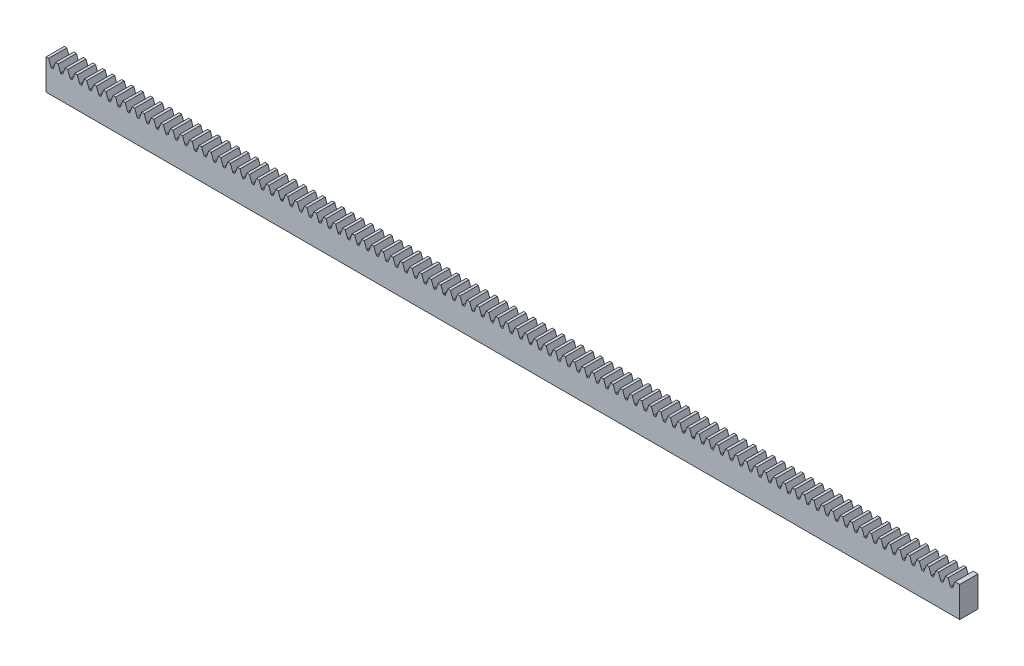
SolidWorks part; units mm, degrees
ref_plane "Front Plane" through (0, 0, 0) normal (0, 0, 1) x (1, 0, 0)
ref_plane "Top Plane" through (0, 0, 0) normal (0, 1, 0) x (1, 0, 0)
ref_plane "Right Plane" through (0, 0, 0) normal (1, 0, 0) x (0, 0, -1)
sketch "Layout Sketch" plane through (0, 0, 0) normal (0, 0, 1) x (1, 0, 0)
  line L0 (0, 0) -> (-150, 0) construction
  line L1 (0, 0) -> (150, 0) construction
  line L2 (0, 0) -> (0, 10) construction
  line L3 (-150, 9) -> (150, 9) construction
  point P3 (495.16, 0)
  point P7 (0, 10)
sketch "Sketch2" plane through (0, 0, 0) normal (1, 0, 0) x (0, 0, -1)
  line L0 (0, 0) -> (0, 10) construction
  line L1 (3, 10) -> (-3, 10)
  line L2 (0, 5) -> (-3, 5) construction
  line L3 (0, 5) -> (3, 5) construction
  line L4 (-3, 10) -> (-3, 0)
  line L5 (-3, 0) -> (3, 0)
  line L6 (3, 0) -> (3, 10)
  dimension "Width" = 6
extrude "Boss-Extrude1" add sketch "Sketch2" along normal up to vertex (150 mm away) and the other way up to vertex (150 mm away) up to point (150, 0, 0) other way up to point (-150, 0, 0)
sketch "Tooth Cut Sketch" plane through (0, 0, 0) normal (0, 0, 1) x (1, 0, 0)
  line L0 (-149.1571, 10) -> (-148.3379, 7.7492)
  line L2 (-148.3379, 7.7492) -> (-147.6776, 7.7492)
  line L3 (-147.6776, 7.7492) -> (-146.8584, 10)
  line L4 (-149.1571, 10) -> (-146.8584, 10)
  line L5 (-149.1571, 10) -> (-150, 10) construction
  line L6 (-146.8584, 10) -> (-146.0155, 10) construction
  line L7 (-146.0155, 10) -> (-145.1963, 7.7492) construction
  line L8 (-148.0078, 7.7492) -> (-148.0078, 10) construction
  line L9 (-148.7932, 9) -> (-147.2224, 9) construction
  line L10 (-147.2224, 9) -> (-147.2224, 10) construction
  line L11 (-145.6516, 9) -> (-145.6516, 7.7492) construction
  line L12 (-147.2224, 9) -> (-145.6516, 9) construction
  line L13 (-150, 10) -> (-150, 0) construction
  line L14 (150, 10) -> (-150, 10) construction
  dimension "D1" = 20
  dimension "D2" = 20
  dimension "D3" = 2.2508
  dimension "D4" = 1
  dimension "D5" = 3.1416
  dimension "D6" = 0.6603
  dimension "D7" = 0.8429
extrude "Tooth Cut" cut sketch "Tooth Cut Sketch" against normal through all both and the other way through all
fillet "Fillet1" radius 0.1981 2 edges at (-147.6776, 7.7492, 0) (-148.3379, 7.7492, 0)
pattern_linear "LPattern1" count 95 spacing 3.1416 along (1, 0, 0) of "Tooth Cut", "Fillet1"
equation "\"D3@Tooth Cut Sketch\" =  ( 2.2 / \"Diametral Pitch@Layout Sketch\" )  + .002"
equation "\"D4@Tooth Cut Sketch\" = 1 / \"Diametral Pitch@Layout Sketch\""
equation "\"D5@Tooth Cut Sketch\" = 3.1416 / \"Diametral Pitch@Layout Sketch\""
equation "\"D1@Fillet1\"= \"D6@Tooth Cut Sketch\" * .3"
equation "\"D3@LPattern1\" = \"D5@Tooth Cut Sketch\""
equation "\"D1@LPattern1\" = \"Overall Length@Layout Sketch\" * 11"
